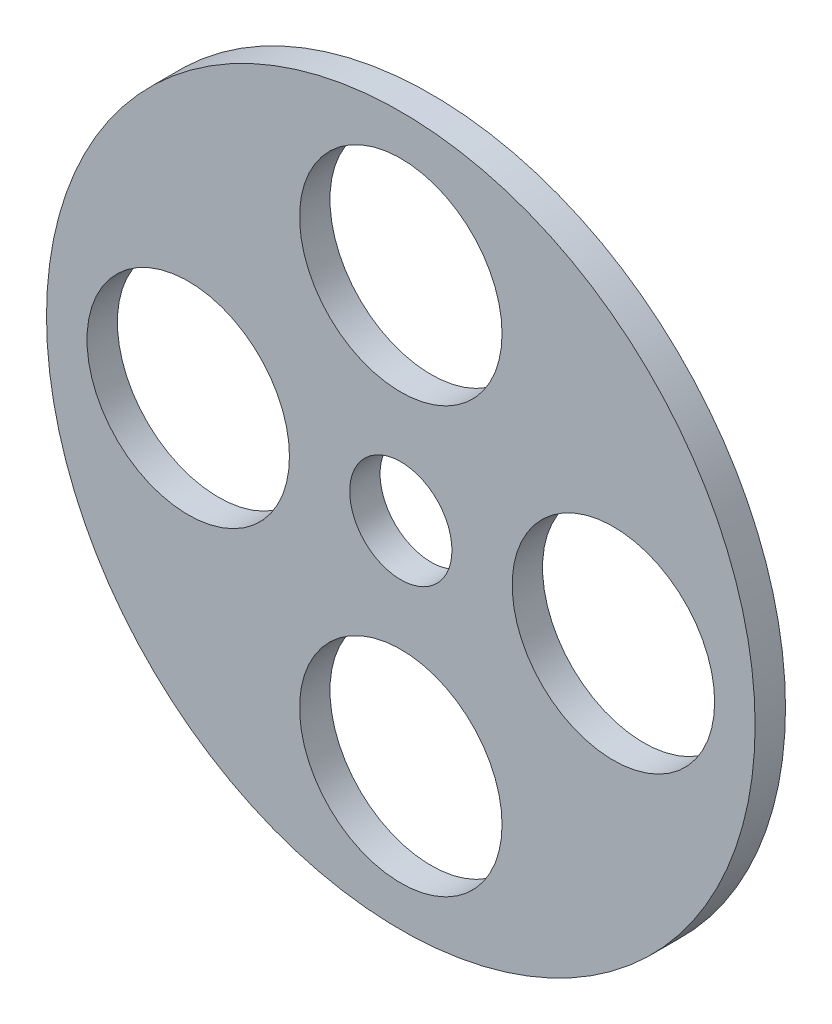
SolidWorks part; units mm, degrees
material "Plywood"
ref_plane "Plan de face" through (0, 0, 0) normal (0, 0, 1) x (1, 0, 0)
ref_plane "Plan de dessus" through (0, 0, 0) normal (0, 1, 0) x (1, 0, 0)
ref_plane "Plan de droite" through (0, 0, 0) normal (1, 0, 0) x (0, 0, -1)
sketch "Esquisse1" plane through (0, 0, 0) normal (0, 0, 1) x (1, 0, 0)
  line L0 (0, 0) -> (0, 21) construction
  circle A0 centre (0, 0) radius 35
  circle A1 centre (0, 0) radius 5.05
  circle A2 centre (0, 21) radius 10
  circle A3 centre (21, 0) radius 10
  circle A4 centre (0, -21) radius 10
  circle A5 centre (-21, 0) radius 10
  point P15 (0, 0)
  dimension "D1" = 10.1
  dimension "D2" = 70
  dimension "D3" = 20
  dimension "D4" = 21
  dimension "D5" = 4
extrude "Boss.-Extru.1" add sketch "Esquisse1" along normal blind 3
